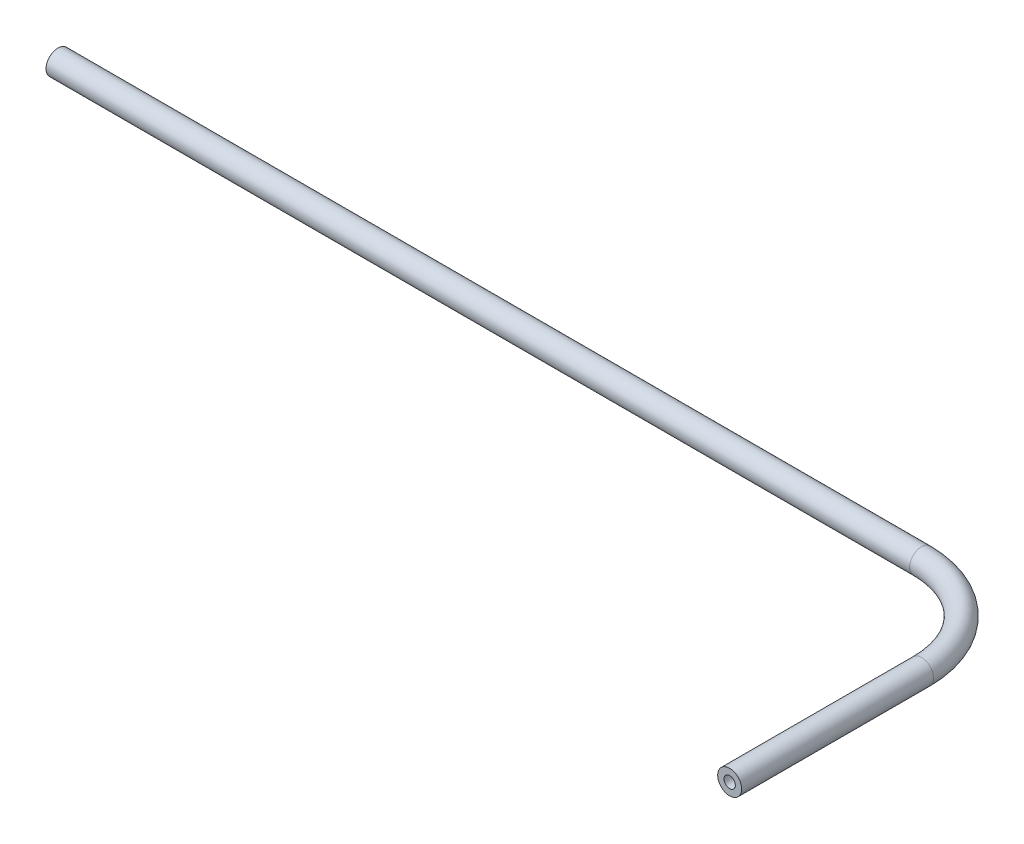
SolidWorks part; units mm, degrees
ref_plane "Front Plane" through (0, 0, 0) normal (0, 0, 1) x (1, 0, 0)
ref_plane "Top Plane" through (0, 0, 0) normal (0, 1, 0) x (1, 0, 0)
ref_plane "Right Plane" through (0, 0, 0) normal (1, 0, 0) x (0, 0, -1)
sketch "Sketch1" plane through (0, 0, 0) normal (0, 1, 0) x (1, 0, 0)
  line L0 (-254, 0) -> (-25.4, 0)
  line L1 (-55, 0) -> (55, 0) construction
  line L2 (0, -25.4) -> (0, -76.2)
  line L3 (0, -55) -> (0, 55) construction
  arc A0 (0, -25.4) -> (-25.4, 0) centre (-25.4, -25.4) ccw
  dimension "D3" = 50.8
  dimension "D1" = 228.6
  dimension "D2" = 50.8
ref_plane "Plane1" through (-254, 0, 0) normal (1, 0, 0) x (0, 0, -1)
sketch "Sketch2" plane through (-254, 0, 0) normal (1, 0, 0) x (0, 0, -1)
  circle A0 centre (0, 0) radius 3.175
  circle A1 centre (0, 0) radius 1.5
  dimension "D1" = 6.35
  dimension "D2" = 3
sweep "Sweep1" add profiles "Sketch2" path "Sketch1"
